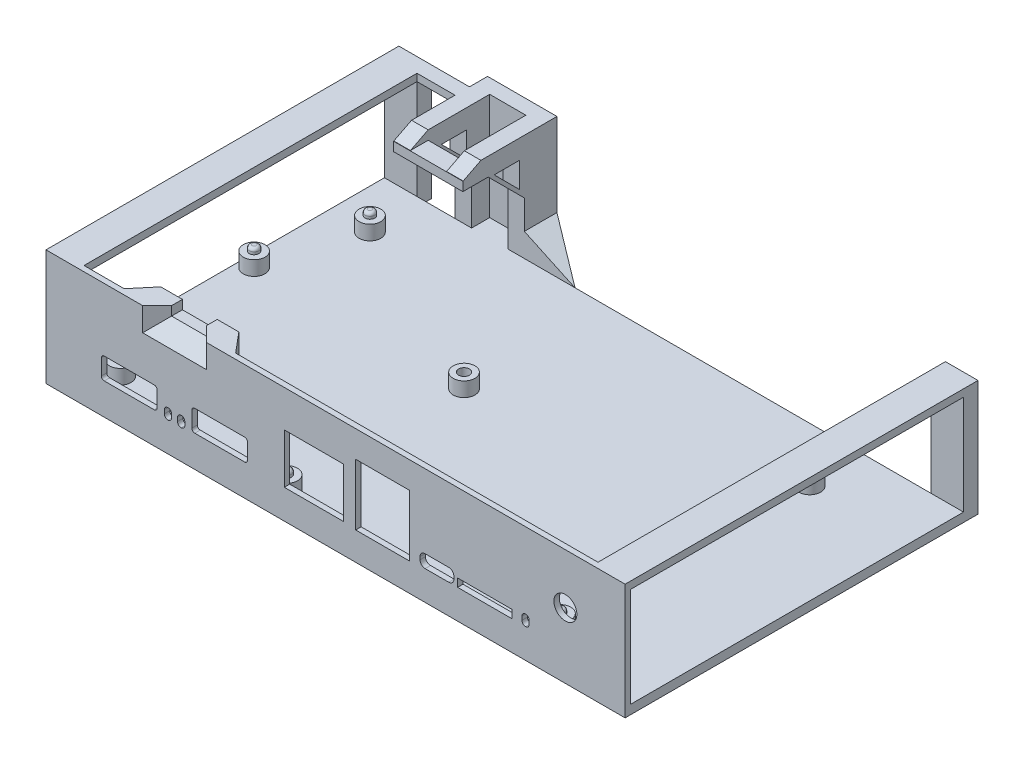
SolidWorks part; units mm, degrees
ref_plane "Front Plane" through (0, 0, 0) normal (0, 0, 1) x (1, 0, 0)
ref_plane "Top Plane" through (0, 0, 0) normal (0, 1, 0) x (1, 0, 0)
ref_plane "Right Plane" through (0, 0, 0) normal (1, 0, 0) x (0, 0, -1)
sketch "Sketch1" plane through (0, 0, 0) normal (0, 1, 0) x (1, 0, 0)
  line L0 (34.5, 92) -> (160, 92)
  line L1 (0, 0) -> (160, 0)
  line L2 (0, 0) -> (0, 92)
  line L3 (0, 92) -> (24, 92)
  line L4 (160, 0) -> (160, 92)
  line L6 (24, 92) -> (24, 99)
  line L7 (24, 99) -> (34.5, 99)
  line L8 (34.5, 92) -> (34.5, 99)
  dimension "D1" = 160
  dimension "D2" = 92
  dimension "D3" = 7
  dimension "D4" = 10.5
  dimension "D5" = 24
extrude "Boss-Extrude1" add sketch "Sketch1" along normal blind 2.5
sketch "Sketch3" plane through (0, 0, 0) normal (0, 1, 0) x (1, 0, 0)
  line L1 (0, 0) -> (160, 0)
  line L2 (0, 0) -> (0, -1.5)
  line L3 (0, -1.5) -> (160, -1.5)
  line L4 (160, 0) -> (160, -1.5)
  dimension "D1" = 1.5
  dimension "D2" = 160
extrude "Boss-Extrude2" add sketch "Sketch3" along normal blind 32
sketch "Sketch4" plane through (0, 2.5, 0) normal (0, 1, 0) x (1, 0, 0)
  line L0 (160, 0) -> (0, 0) construction
  line L1 (0, 92) -> (0, 0) construction
  line L2 (0, 0) -> (160, 0) construction
  circle A0 centre (11, 8) radius 3
  circle A1 centre (11, 77) radius 3
  circle A2 centre (61.5, 3.5) radius 3
  circle A3 centre (132.5, 8) radius 3
  circle A4 centre (132.5, 77) radius 3
  circle A5 centre (3.5, 52.5) radius 3
  circle A6 centre (61.5, 52.5) radius 3
  dimension "D1" = 8
  dimension "D3" = 77
  dimension "D4" = 61.5
  dimension "D5" = 132.5
  dimension "D6" = 52.5
  dimension "D8" = 3.5
  dimension "D2" = 11
  dimension "D7" = 3.5
extrude "Boss-Extrude3" add sketch "Sketch4" along normal blind 4
sketch "Sketch6" plane through (0, 6.5, 0) normal (0, 1, 0) x (1, 0, 0)
  circle A0 centre (11, 77) radius 1.33
  circle A1 centre (3.5, 52.5) radius 1.33
  circle A2 centre (11, 8) radius 1.33
  circle A3 centre (61.5, 3.5) radius 1.33
  circle A4 centre (132.5, 8) radius 1.33
  circle A5 centre (132.5, 77) radius 1.33
extrude "Boss-Extrude5" add sketch "Sketch6" along normal blind 1.5
sketch "Sketch7" plane through (0, 6.5, 0) normal (0, 1, 0) x (1, 0, 0)
  circle A0 centre (61.5, 52.5) radius 1.5
extrude "Cut-Extrude1" cut sketch "Sketch7" against normal blind 4
sketch "Sketch8" plane through (0, 0, 0) normal (0, 1, 0) x (1, 0, 0)
  line L0 (24, 92) -> (0, 92) construction
  line L1 (19.5, 92) -> (24.0826, 92)
  line L2 (19.5, 92) -> (19.5, 99)
  line L4 (24.0826, 92) -> (24.0826, 97)
  line L6 (34.0826, 92) -> (38.6652, 92)
  line L7 (34.0826, 92) -> (34.0826, 97)
  line L9 (38.6652, 92) -> (38.6652, 99)
  line L10 (24.0826, 97) -> (34.0826, 97)
  line L11 (19.5, 99) -> (19.5, 101)
  line L12 (19.5, 101) -> (38.6652, 101)
  line L13 (38.6652, 99) -> (38.6652, 101)
  dimension "D1" = 19.5
  dimension "D2" = 5
  dimension "D3" = 5
  dimension "D4" = 10
  dimension "D5" = 7
  dimension "D6" = 7
  dimension "D7" = 2
extrude "Boss-Extrude6" add sketch "Sketch8" along normal blind 32
sketch "Sketch10" plane through (0, 0, 0) normal (0, 1, 0) x (1, 0, 0)
  line L6 (38.6652, 101) -> (38.6652, 92)
  line L7 (38.6652, 92) -> (52.6652, 92)
  line L8 (160, 92) -> (38.6652, 92) construction
  line L9 (52.6652, 92) -> (38.6652, 101)
  dimension "D2" = 14
extrude "Boss-Extrude7" add sketch "Sketch10" along normal blind 2.5
chamfer "Chamfer2" distance 6.5 angle 65 1 edges at (38.6652, 2.5, -96.5) first distance on face at (38.6652, 17.25, -96.5)
sketch "Sketch11" plane through (0, 0, 1.5) normal (0, 0, 1) x (1, 0, 0)
  line L0 (0, 0) -> (160, 0) construction
  line L1 (15.3, 14.63) -> (30.7, 14.63)
  line L2 (15.3, 14.63) -> (15.3, 8.68)
  line L3 (15.3, 8.68) -> (30.7, 8.68)
  line L4 (30.7, 14.63) -> (30.7, 8.68)
  line L5 (0, 32) -> (0, 0) construction
  line L6 (0, 32) -> (160, 32) construction
  line L7 (40.3, 8.68) -> (55.7, 8.68)
  line L8 (40.3, 8.68) -> (40.3, 14.63)
  line L9 (40.3, 14.63) -> (55.7, 14.63)
  line L10 (55.7, 8.68) -> (55.7, 14.63)
  line L11 (65.84, 8.1) -> (82.17, 8.1)
  line L12 (65.84, 8.1) -> (65.84, 21.84)
  line L13 (65.84, 21.84) -> (82.17, 21.84)
  line L14 (82.17, 8.1) -> (82.17, 21.84)
  line L15 (85.56, 7.75) -> (100.46, 7.75)
  line L16 (85.56, 7.75) -> (85.56, 24.67)
  line L17 (85.56, 24.67) -> (100.46, 24.67)
  line L18 (100.46, 7.75) -> (100.46, 24.67)
  line L19 (103.34, 11.66) -> (112.68, 11.66)
  line L20 (103.34, 11.66) -> (103.34, 8.1)
  line L21 (103.34, 8.1) -> (112.68, 8.1)
  line L22 (112.68, 11.66) -> (112.68, 8.1)
  line L23 (113.71, 10.35) -> (128.81, 10.35)
  line L24 (113.71, 10.35) -> (113.71, 8.1)
  line L25 (113.71, 8.1) -> (128.81, 8.1)
  line L26 (128.81, 10.35) -> (128.81, 8.1)
  line L27 (32.7, 8.1) -> (34.7, 8.1)
  line L28 (32.7, 8.1) -> (32.7, 11.1)
  line L29 (32.7, 11.1) -> (34.7, 11.1)
  line L30 (34.7, 8.1) -> (34.7, 11.1)
  line L31 (36.35, 8.1) -> (38.35, 8.1)
  line L32 (36.35, 8.1) -> (36.35, 11.1)
  line L33 (36.35, 11.1) -> (38.35, 11.1)
  line L34 (38.35, 8.1) -> (38.35, 11.1)
  line L35 (131.5, 8.1) -> (133.5, 8.1)
  line L36 (131.5, 8.1) -> (131.5, 11.1)
  line L37 (131.5, 11.1) -> (133.5, 11.1)
  line L38 (133.5, 8.1) -> (133.5, 11.1)
  line L39 (30.7, 32) -> (40.3, 32)
  line L40 (30.7, 32) -> (30.7, 29.5)
  line L41 (30.7, 29.5) -> (40.3, 29.5)
  line L42 (40.3, 32) -> (40.3, 29.5)
  circle A0 centre (143.5, 18.1) radius 3.175
  point P48 (0, 0)
  dimension "D39" = 6.35
  dimension "D1" = 15.4
  dimension "D2" = 5.95
  dimension "D3" = 8.68
  dimension "D4" = 15.3
  dimension "D5" = 9.6
  dimension "D6" = 5.95
  dimension "D7" = 15.4
  dimension "D8" = 8.68
  dimension "D9" = 16.33
  dimension "D10" = 13.74
  dimension "D11" = 8.1
  dimension "D12" = 10.14
  dimension "D13" = 3.39
  dimension "D14" = 16.92
  dimension "D15" = 14.9
  dimension "D16" = 7.75
  dimension "D17" = 3.56
  dimension "D18" = 9.34
  dimension "D19" = 2.88
  dimension "D20" = 8.1
  dimension "D21" = 1.03
  dimension "D22" = 15.1
  dimension "D23" = 2.25
  dimension "D24" = 8.1
  dimension "D25" = 2
  dimension "D26" = 3
  dimension "D27" = 8.1
  dimension "D28" = 32.7
  dimension "D29" = 2
  dimension "D30" = 3
  dimension "D31" = 8.1
  dimension "D32" = 1.65
  dimension "D33" = 2
  dimension "D34" = 3
  dimension "D35" = 131.5
  dimension "D36" = 9.6
  dimension "D37" = 15.4
  dimension "D38" = 2.5
  dimension "D40" = 10
  dimension "D41" = 10
extrude "Cut-Extrude2" cut sketch "Sketch11" against normal up to next
fillet "Fillet1" radius 1.4 4 edges at (103.34, 8.1, 0.75) (103.34, 11.66, 0.75) (112.68, 11.66, 0.75) (112.68, 8.1, 0.75)
fillet "Fillet2" radius 0.8 8 edges at (30.7, 14.63, 0.75) (30.7, 8.68, 0.75) (15.3, 8.68, 0.75) (15.3, 14.63, 0.75) (40.3, 8.68, 0.75) (40.3, 14.63, 0.75) (55.7, 8.68, 0.75) (55.7, 14.63, 0.75)
fillet "Fillet3" radius 0.8 6 edges at (132.5, 8, -6.67) (132.5, 8, -75.67) (11, 8, -75.67) (3.5, 8, -51.17) (61.5, 8, -2.17) (11, 8, -6.67)
fillet "Fillet4" radius 1 12 edges at (34.7, 8.1, 0.75) (38.35, 8.1, 0.75) (38.35, 11.1, 0.75) (34.7, 11.1, 0.75) (32.7, 8.1, 0.75) (36.35, 8.1, 0.75) (36.35, 11.1, 0.75) (32.7, 11.1, 0.75) (131.5, 11.1, 0.75) (133.5, 11.1, 0.75) (131.5, 8.1, 0.75) (133.5, 8.1, 0.75)
sketch "Sketch12" plane through (0, 0, 0) normal (0, 0, -1) x (-1, 0, 0)
  line L0 (-160, 32) -> (-40.3, 32) construction
  line L1 (-40.3, 29.5) -> (-30.7, 29.5)
  line L3 (-40.3, 26.5) -> (-30.7, 26.5)
  line L5 (-40.3, 26.5) -> (-46.3, 26.5)
  line L6 (-40.3, 29.5) -> (-40.3, 32)
  line L7 (-40.3, 32) -> (-46.3, 32)
  line L8 (-46.3, 26.5) -> (-46.3, 32)
  line L9 (-30.7, 32) -> (0, 32) construction
  line L10 (-30.7, 26.5) -> (-24.7, 26.5)
  line L11 (-30.7, 29.5) -> (-30.7, 32)
  line L12 (-30.7, 32) -> (-24.7, 32)
  line L13 (-24.7, 26.5) -> (-24.7, 32)
  dimension "D1" = 9.6
  dimension "D2" = 3
  dimension "D3" = 6
  dimension "D4" = 6
extrude "Boss-Extrude8" add sketch "Sketch12" along normal blind 5.5
chamfer "Chamfer3" distance 5.5 angle 45 1 edges at (35.5, 26.5, 0)
chamfer "Chamfer4" distance 4.6 angle 50 2 edges at (46.3, 26.5, 0) (24.7, 26.5, 0) first distance on face at (23, 11.655, 0)
chamfer "Chamfer5" distance 4 angle 45 3 edges at (40.3, 30.75, 1.5) (35.5, 29.5, 1.5) (30.7, 30.75, 1.5)
sketch "Sketch13" plane through (0, 32, 0) normal (0, 1, 0) x (1, 0, 0)
  line L5 (19.5, 92) -> (24.0826, 92)
  line L6 (19.5, 92) -> (19.5, 80)
  line L7 (19.5, 80) -> (24.0826, 80)
  line L8 (24.0826, 92) -> (24.0826, 80)
  line L13 (34.0826, 92) -> (38.6652, 92)
  line L14 (34.0826, 92) -> (34.0826, 80)
  line L15 (34.0826, 80) -> (38.6652, 80)
  line L16 (38.6652, 92) -> (38.6652, 80)
  dimension "D1" = 12
  dimension "D2" = 4.5826
  dimension "D3" = 4.5826
  dimension "D4" = 12
extrude "Boss-Extrude9" add sketch "Sketch13" against normal blind 5
sketch "Sketch16" plane through (0, 0, -80) normal (0, 0, 1) x (1, 0, 0)
  line L1 (19.5, 27) -> (38.6652, 27)
  line L2 (19.5, 27) -> (19.5, 29.5)
  line L3 (19.5, 29.5) -> (38.6652, 29.5)
  line L4 (38.6652, 27) -> (38.6652, 29.5)
  point P7 (0, 0)
  dimension "D1" = 2.5
extrude "Boss-Extrude10" add sketch "Sketch16" along normal blind 5
chamfer "Chamfer6" distance 2.5 angle 63 2 edges at (21.7913, 29.5, -80) (36.3739, 29.5, -80) first distance on face at (21.7913, 30.75, -80) first distance on face at (36.3739, 30.75, -80)
chamfer "Chamfer7" distance 10 angle 45 2 edges at (21.7913, 27, -92) (36.3739, 27, -92)
sketch "Sketch17" plane through (19.5, 0, 0) normal (-1, 0, 0) x (0, 0, 1)
  line L0 (-90.6584, 19.6833) -> (-90.6584, 26.6833)
  line L1 (-90.6584, 26.6833) -> (-83.6584, 26.6833)
  line L2 (-83.6584, 26.6833) -> (-90.6584, 19.6833)
  dimension "D1" = 7
  dimension "D2" = 7
  dimension "D3" = 3
extrude "Cut-Extrude3" cut sketch "Sketch17" against normal blind 20
sketch "Sketch18" plane through (0, 0, 0) normal (0, 1, 0) x (1, 0, 0)
  line L1 (0, 92) -> (9, 92)
  line L2 (0, 92) -> (0, 96)
  line L3 (0, 96) -> (9, 96)
  line L4 (9, 92) -> (9, 96)
  line L5 (160, 92) -> (151, 92)
  line L6 (160, 92) -> (160, 96)
  line L7 (160, 96) -> (151, 96)
  line L8 (151, 92) -> (151, 96)
  dimension "D1" = 9
  dimension "D2" = 4
  dimension "D3" = 9
  dimension "D4" = 4
extrude "Boss-Extrude11" add sketch "Sketch18" along normal blind 30
sketch "Sketch19" plane through (0, 30, 0) normal (0, 1, 0) x (1, 0, 0)
  line L0 (0, 0) -> (160, 0) construction
  line L1 (0, 96) -> (9, 96)
  line L2 (0, 96) -> (0, 0)
  line L3 (0, 0) -> (9, 0)
  line L4 (9, 92) -> (9, 0)
  line L5 (19.5, 101) -> (19.5, 80) construction
  line L6 (151, 96) -> (160, 96)
  line L7 (151, 96) -> (151, 0)
  line L8 (151, 0) -> (160, 0)
  line L9 (160, 96) -> (160, 0)
  line L10 (9, 96) -> (19.5, 96)
  line L12 (9, 92) -> (19.5, 92)
  line L13 (19.5, 96) -> (19.5, 92)
  line L14 (19.5, 92) -> (9, 92) construction
  dimension "D1" = 9
extrude "Boss-Extrude12" add sketch "Sketch19" along normal blind 2
